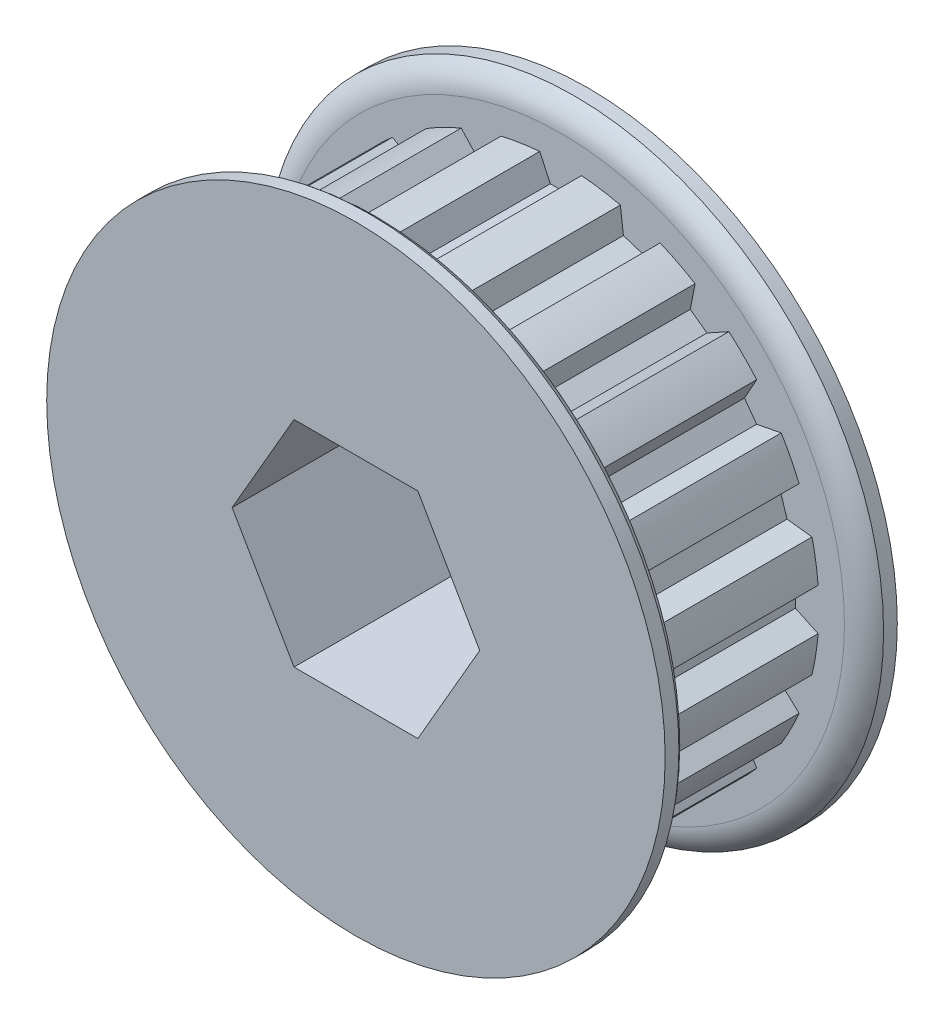
SolidWorks part; units mm, degrees
ref_plane "Front Plane" through (0, 0, 0) normal (0, 0, 1) x (1, 0, 0)
ref_plane "Top Plane" through (0, 0, 0) normal (0, 1, 0) x (1, 0, 0)
ref_plane "Right Plane" through (0, 0, 0) normal (1, 0, 0) x (0, 0, -1)
sketch "Sketch1" plane through (0, 0, 0) normal (0, 0, 1) x (1, 0, 0)
  line L0 (-1.2878, 15.8609) -> (-0.635, 14.4609)
  line L1 (-0.635, 14.4609) -> (0.635, 14.4609)
  line L2 (0.635, 14.4609) -> (1.2878, 15.8609)
  line L3 (-1.2878, 15.8609) -> (1.2878, 15.8609)
  line L4 (0, 0) -> (0, 14.4609) construction
  line L5 (0, 14.4609) -> (0, 16.7469) construction
  circle A0 centre (0, 0) radius 16.1671 construction
  circle A1 centre (0, 0) radius 19.05 construction
  circle A2 centre (0, 0) radius 15.9131 construction
  point P6 (0, 15.8609)
  point P11 (0, 16.1671)
  point P13 (0, 19.05)
  point P14 (0, 15.9131)
  dimension "D1" = 1.4
  dimension "PD" = 32.3342
  dimension "OD" = 38.1
  dimension "D3" = 1.27
  dimension "Gear OD" = 31.8262
  dimension "b" = 50
  dimension "hs" = 2.286
sketch "Sketch2" plane through (0, 0, 0) normal (1, 0, 0) x (0, 0, -1)
  line L0 (-11.1125, 6.35) -> (11.1125, 6.35)
  line L1 (-11.1125, 6.35) -> (-11.1125, 11.8999)
  line L2 (-11.1125, 11.8999) -> (-3.1877, 11.8999)
  line L3 (-3.1877, 11.8999) -> (-3.1877, 19.05)
  line L4 (-3.1877, 19.05) -> (-1.4986, 19.05) construction
  line L5 (-1.4986, 19.05) -> (-1.4986, 15.9131) construction
  line L6 (-1.4986, 15.9131) -> (9.4234, 15.9131)
  line L7 (9.4234, 15.9131) -> (9.4234, 19.05) construction
  line L8 (9.4234, 19.05) -> (11.1125, 19.05) construction
  line L9 (11.1125, 19.05) -> (11.1125, 6.35)
  line L10 (-11.1125, 0) -> (11.1125, 0) construction
  line L13 (-3.1877, 19.05) -> (-2.3432, 19.05)
  line L14 (-1.4986, 17.4815) -> (-1.4986, 15.9131)
  line L15 (9.4234, 15.9131) -> (9.4234, 17.4815)
  line L16 (10.2679, 19.05) -> (11.1125, 19.05)
  arc A0 (-1.4986, 17.4815) -> (-2.3432, 19.05) centre (-3.3773, 17.4815) ccw
  arc A1 (9.4234, 17.4815) -> (10.2679, 19.05) centre (11.3021, 17.4815) cw
  point P12 (-1.4986, 17.4815)
  point P14 (-2.3432, 19.05)
  point P20 (9.4234, 17.4815)
  point P21 (10.2679, 19.05)
  point P25 (9.4234, 0)
  point P26 (-1.4986, 0)
  dimension "OA" = 22.225
  dimension "Bore" = 12.7
  dimension "Hub Dia" = 23.7998
  dimension "Outside Width" = 14.3002
  dimension "Inside Width" = 10.922
revolve "Revolve1" add sketch "Sketch2" angle 360 mid plane about L10
sketch "Sketch3" plane through (0, 0, 0) normal (0, 0, 1) x (1, 0, 0)
  line L0 (-0.635, 14.4609) -> (0.635, 14.4609) construction
  line L1 (0.635, 14.4609) -> (1.2878, 15.8609) construction
  line L2 (-1.2878, 15.8609) -> (-0.635, 14.4609) construction
  line L3 (-0.635, 14.4609) -> (0.635, 14.4609)
  line L4 (0.635, 14.4609) -> (1.2878, 15.8609)
  line L5 (-1.2878, 15.8609) -> (-0.635, 14.4609)
  circle A0 centre (0, 0) radius 15.9131 construction
  arc A1 (1.2878, 15.8609) -> (-1.2878, 15.8609) centre (0, 0) ccw
extrude "Cut-Extrude1" cut sketch "Sketch3" against normal up to vertex (9.4234 mm away) from vertex up to point (0, 15.9131, -9.4234) starting at point (0, 15.9131, 1.4986)
fillet "Fillet1" [suppressed] radius 0.61
pattern_circular "CirPattern1" count 20 over 360 about axis through (0, 0, 11.1125) along (0, 0, 1) of "Cut-Extrude1", "Fillet1"
sketch "Sketch4" plane through (0, 0, 0) normal (0, 1, 0) x (1, 0, 0)
  line L0 (0, -3.9878) -> (0, -10.3124) construction
  circle A0 centre (0, -7.1501) radius 2.3813
  dimension "D1" = 4.7625
extrude "Cut-Extrude2" cut sketch "Sketch4" along normal through all
ref_plane "Plane1" through (0, 0, 7.1501) normal (0, 0, 1) x (1, 0, 0)
sketch "Sketch5" plane through (0, 0, 7.1501) normal (0, 0, 1) x (1, 0, 0)
  line L0 (0, 0) -> (0, 11.8999) construction
  line L1 (1.8733, 11.6592) -> (2.3812, 11.1512)
  line L2 (0, 11.6592) -> (1.8733, 11.6592)
  line L3 (0, 11.6592) -> (0, 6.35)
  line L4 (0, 6.35) -> (1.7463, 6.35)
  line L5 (2.3812, 11.1512) -> (2.3812, 6.985)
  line L6 (1.7463, 6.35) -> (2.3812, 6.985)
  circle A0 centre (0, 0) radius 11.8999 construction
  circle A1 centre (0, 0) radius 6.35 construction
  point P7 (2.3813, 6.35)
  point P9 (2.3813, 11.6592)
revolve "Revolve2" add sketch "Sketch5" angle 360 mid plane about L0
sketch "Sketch6" plane through (0, 11.6592, 0) normal (0, 1, 0) x (1, 0, 0)
  line L1 (0, -5.7753) -> (-1.1906, -6.4627)
  line L2 (-1.1906, -6.4627) -> (-1.1906, -7.8375)
  line L3 (-1.1906, -7.8375) -> (0, -8.5249)
  line L4 (0, -8.5249) -> (1.1906, -7.8375)
  line L5 (1.1906, -7.8375) -> (1.1906, -6.4627)
  line L6 (1.1906, -6.4627) -> (0, -5.7753)
  circle A0 centre (0, -7.1501) radius 1.1906 construction
  dimension "D1" = 2.3813
extrude "Cut-Extrude3" cut sketch "Sketch6" against normal blind 1.7859
pattern_circular "CirPattern2" count 2 every 90 of "Cut-Extrude2", "Revolve2", "Cut-Extrude3"
ref_plane "Contact Plane 1" through (0, 0, 11.1125) normal (0, 0, 1) x (1, 0, 0)
ref_plane "Contact Plane 2" through (0, 0, -11.1125) normal (0, 0, -1) x (-1, 0, 0)
ref_axis "Center Axis 1" through (0, 0, -11.1125) along (0, 0, 1)
sketch "Sketch7" plane through (0, 0, -11.1125) normal (0, 0, -1) x (-1, 0, 0)
  line L1 (3.8128, -6.604) -> (7.6256, 0)
  line L2 (7.6256, 0) -> (3.8128, 6.604)
  line L3 (3.8128, 6.604) -> (-3.8128, 6.604)
  line L4 (-3.8128, 6.604) -> (-7.6256, 0)
  line L5 (-7.6256, 0) -> (-3.8128, -6.604)
  line L6 (-3.8128, -6.604) -> (3.8128, -6.604)
  circle A0 centre (0, 0) radius 6.604 construction
  dimension "D1" = 13.208
extrude "Cut-Extrude4" cut sketch "Sketch7" against normal through all
sketch "Sketch8" plane through (0, 0, 3.1877) normal (0, 0, 1) x (1, 0, 0)
  circle A0 centre (0, 0) radius 14.5091
extrude "Cut-Extrude5" cut sketch "Sketch8" along normal through all
equation "\"D1@Sketch6\" = \"D1@Sketch4\"/2"
equation "\"D1@Cut-Extrude3\" = \"D1@Sketch6\"*.75"
